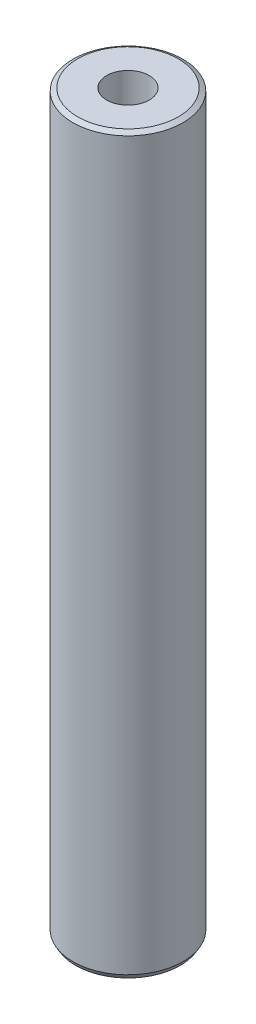
SolidWorks part; units mm, degrees
ref_plane "Front Plane" through (0, 0, 0) normal (0, 0, 1) x (1, 0, 0)
ref_plane "Top Plane" through (0, 0, 0) normal (0, 1, 0) x (1, 0, 0)
ref_plane "Right Plane" through (0, 0, 0) normal (1, 0, 0) x (0, 0, -1)
sketch "Sketch1" plane through (0, 0, 0) normal (0, 1, 0) x (1, 0, 0)
  circle A0 centre (0, 0) radius 45
  dimension "SHAFT_OD" = 90
extrude "Boss-Extrude1" add sketch "Sketch1" along normal blind 600
sketch "Sketch2" plane through (0, 0, 0) normal (0, 1, 0) x (1, 0, 0)
  circle A0 centre (0, 0) radius 17.4138
  dimension "BORE_D" = 34.8275
extrude "Cut-Extrude1" cut sketch "Sketch2" along normal through all
chamfer "Chamfer1" distance 2.2233 angle 60 2 edges at (0, 600, 45) (0, 0, 45) first distance on face at (0, 600, 45) first distance on face at (0, 0, 17.4138)
